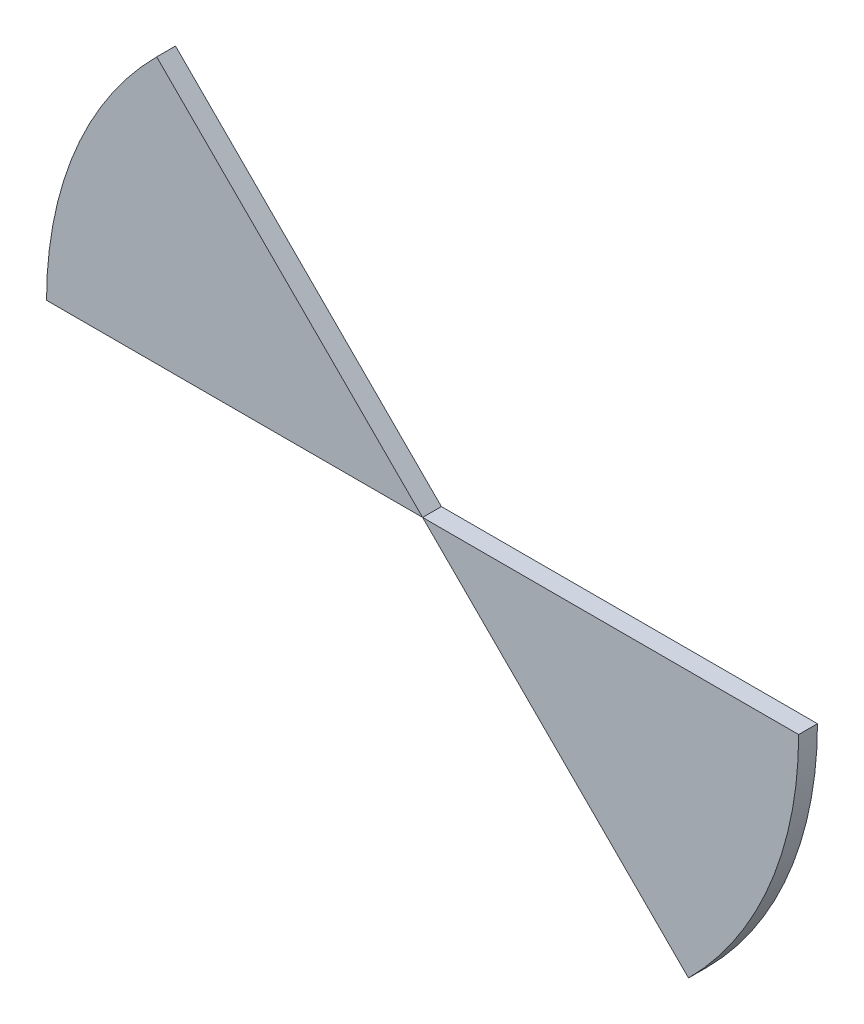
SolidWorks part; units mm, degrees
ref_plane "Front Plane" through (0, 0, 0) normal (0, 0, 1) x (1, 0, 0)
ref_plane "Top Plane" through (0, 0, 0) normal (0, 1, 0) x (1, 0, 0)
ref_plane "Right Plane" through (0, 0, 0) normal (1, 0, 0) x (0, 0, -1)
sketch "Sketch1" plane through (0, 0, 0) normal (0, 0, 1) x (1, 0, 0)
  line L1 (0, 0) -> (-70.7107, 70.7107)
  line L2 (-100, 0) -> (0, 0)
  arc A3 (-70.7107, 70.7107) -> (-100, 0) centre (0, 0) ccw
  dimension "D1" = 100
  dimension "D2" = 45
  dimension "D3" = 0
extrude "Boss-Extrude1" add sketch "Sketch1" along normal blind 5
ref_axis "Axis1" through (0, 0, 32.0444) along (0, 0, -1)
sketch "Sketch2" plane through (0, 0, 0) normal (0, 0, 1) x (1, 0, 0)
  line L0 (0, 0) -> (70.7107, -70.7107)
  line L1 (100, 0) -> (0, 0)
  arc A0 (70.7107, -70.7107) -> (100, 0) centre (0, 0) ccw
  dimension "D1" = 100
  dimension "D2" = 0
  dimension "D3" = 45
extrude "Boss-Extrude2" add sketch "Sketch2" along normal up to surface (5 mm away) separate body up to face at (-59.2478, 24.5412, 5)
